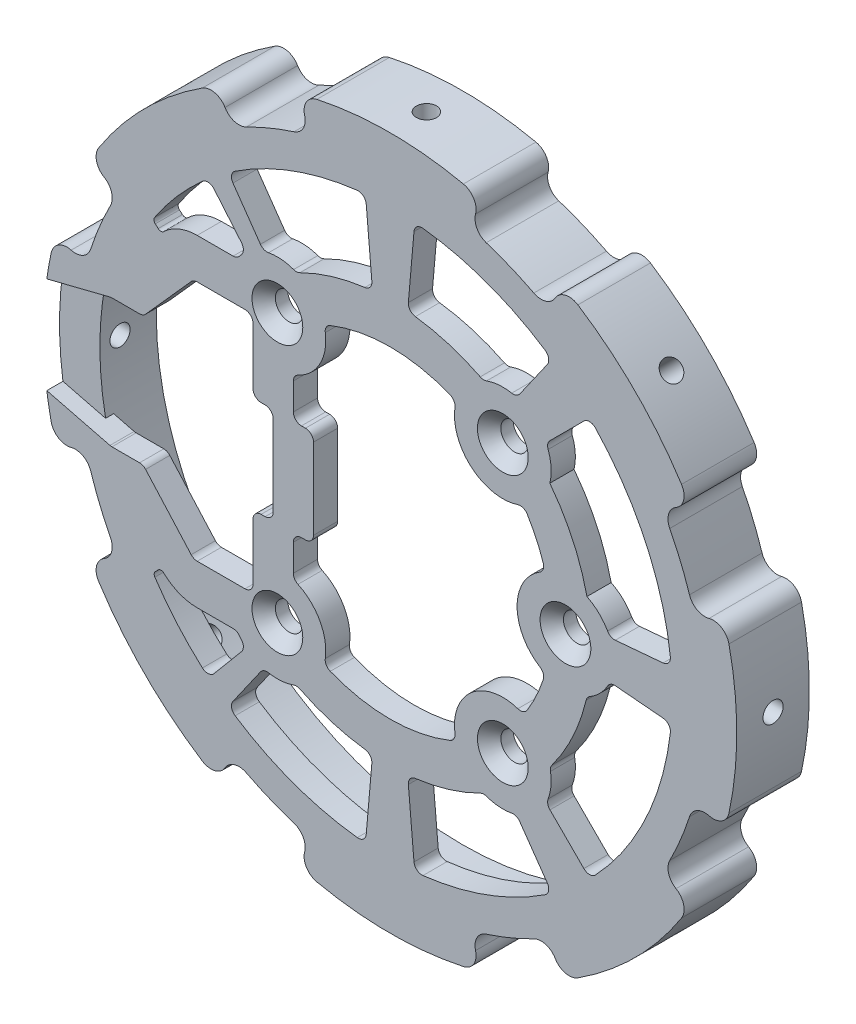
SolidWorks part; units mm, degrees
ref_plane "前视基准面" through (0, 0, 0) normal (0, 0, 1) x (1, 0, 0)
ref_plane "上视基准面" through (0, 0, 0) normal (0, 1, 0) x (1, 0, 0)
ref_plane "右视基准面" through (0, 0, 0) normal (1, 0, 0) x (0, 0, -1)
sketch "草图1" plane through (0, 0, 0) normal (0, 0, 1) x (1, 0, 0)
  line L16 (21.5, 37.2391) -> (19.5, 33.775)
  line L17 (11.1292, 41.5348) -> (10.0939, 37.6711)
  line L18 (-11.1292, 41.5348) -> (-10.0939, 37.6711)
  line L19 (37.2391, 21.5) -> (33.775, 19.5)
  line L20 (41.5348, 11.1292) -> (37.6711, 10.0939)
  line L21 (41.5348, -11.1292) -> (37.6711, -10.0939)
  line L22 (37.2391, -21.5) -> (33.775, -19.5)
  line L23 (21.5, -37.2391) -> (19.5, -33.775)
  line L24 (11.1292, -41.5348) -> (10.0939, -37.6711)
  line L25 (-11.1292, -41.5348) -> (-10.0939, -37.6711)
  line L26 (-21.5, -37.2391) -> (-19.5, -33.775)
  line L27 (-37.2391, -21.5) -> (-33.775, -19.5)
  line L28 (-41.5348, -11.1292) -> (-37.6711, -10.0939)
  line L29 (-41.5348, 11.1292) -> (-37.6711, 10.0939)
  line L30 (-37.2391, 21.5) -> (-33.775, 19.5)
  line L31 (-21.5, 37.2391) -> (-19.5, 33.775)
  circle A1 centre (0, 0) radius 38
  arc A6 (0, 43) -> (-11.1292, 41.5348) centre (0, 0) ccw
  arc A31 (0, 43) -> (11.1292, 41.5348) centre (0, 0) cw
  arc A32 (10.0939, 37.6711) -> (19.5, 33.775) centre (0, 0) cw
  arc A33 (30.4056, 30.4056) -> (21.5, 37.2391) centre (0, 0) ccw
  arc A34 (30.4056, 30.4056) -> (37.2391, 21.5) centre (0, 0) cw
  arc A35 (33.775, 19.5) -> (37.6711, 10.0939) centre (0, 0) cw
  arc A36 (43, 0) -> (41.5348, 11.1292) centre (0, 0) ccw
  arc A37 (43, 0) -> (41.5348, -11.1292) centre (0, 0) cw
  arc A38 (37.6711, -10.0939) -> (33.775, -19.5) centre (0, 0) cw
  arc A39 (30.4056, -30.4056) -> (37.2391, -21.5) centre (0, 0) ccw
  arc A40 (30.4056, -30.4056) -> (21.5, -37.2391) centre (0, 0) cw
  arc A41 (19.5, -33.775) -> (10.0939, -37.6711) centre (0, 0) cw
  arc A42 (0, -43) -> (11.1292, -41.5348) centre (0, 0) ccw
  arc A43 (0, -43) -> (-11.1292, -41.5348) centre (0, 0) cw
  arc A44 (-10.0939, -37.6711) -> (-19.5, -33.775) centre (0, 0) cw
  arc A45 (-30.4056, -30.4056) -> (-21.5, -37.2391) centre (0, 0) ccw
  arc A46 (-30.4056, -30.4056) -> (-37.2391, -21.5) centre (0, 0) cw
  arc A47 (-33.775, -19.5) -> (-37.6711, -10.0939) centre (0, 0) cw
  arc A48 (-43, 0) -> (-41.5348, -11.1292) centre (0, 0) ccw
  arc A49 (-43, 0) -> (-41.5348, 11.1292) centre (0, 0) cw
  arc A50 (-37.6711, 10.0939) -> (-33.775, 19.5) centre (0, 0) cw
  arc A51 (-30.4056, 30.4056) -> (-37.2391, 21.5) centre (0, 0) ccw
  arc A52 (-30.4056, 30.4056) -> (-21.5, 37.2391) centre (0, 0) cw
  arc A53 (-19.5, 33.775) -> (-10.0939, 37.6711) centre (0, 0) cw
  point P55 (0, 0)
  point P56 (0, 0)
  dimension "D1" = 8
extrude "凸台-拉伸1" add sketch "草图1" against normal blind 6
sketch "草图2" plane through (0, 0, 0) normal (0, 0, 1) x (1, 0, 0)
  line L16 (-11.1292, 41.5348) -> (-10.0939, 37.6711)
  line L17 (10.0939, 37.6711) -> (11.1292, 41.5348)
  line L18 (21.5, 37.2391) -> (19.5, 33.775)
  line L19 (33.775, 19.5) -> (37.2391, 21.5)
  line L20 (41.5348, 11.1292) -> (37.6711, 10.0939)
  line L21 (37.6711, -10.0939) -> (41.5348, -11.1292)
  line L22 (37.2391, -21.5) -> (33.775, -19.5)
  line L23 (19.5, -33.775) -> (21.5, -37.2391)
  line L24 (11.1292, -41.5348) -> (10.0939, -37.6711)
  line L25 (-10.0939, -37.6711) -> (-11.1292, -41.5348)
  line L26 (-21.5, -37.2391) -> (-19.5, -33.775)
  line L27 (-33.775, -19.5) -> (-37.2391, -21.5)
  line L28 (-41.5348, -11.1292) -> (-37.6711, -10.0939)
  line L29 (-37.6711, 10.0939) -> (-41.5348, 11.1292)
  line L30 (-37.2391, 21.5) -> (-33.775, 19.5)
  line L31 (-19.5, 33.775) -> (-21.5, 37.2391)
  arc A27 (0, 43) -> (11.1292, 41.5348) centre (0, 0) cw
  arc A28 (10.0939, 37.6711) -> (19.5, 33.775) centre (0, 0) cw
  arc A29 (0, 43) -> (-11.1292, 41.5348) centre (0, 0) ccw
  arc A30 (30.4056, 30.4056) -> (21.5, 37.2391) centre (0, 0) ccw
  arc A31 (30.4056, 30.4056) -> (37.2391, 21.5) centre (0, 0) cw
  arc A32 (33.775, 19.5) -> (37.6711, 10.0939) centre (0, 0) cw
  arc A33 (43, 0) -> (41.5348, 11.1292) centre (0, 0) ccw
  arc A34 (43, 0) -> (41.5348, -11.1292) centre (0, 0) cw
  arc A35 (37.6711, -10.0939) -> (33.775, -19.5) centre (0, 0) cw
  arc A36 (30.4056, -30.4056) -> (37.2391, -21.5) centre (0, 0) ccw
  arc A37 (30.4056, -30.4056) -> (21.5, -37.2391) centre (0, 0) cw
  arc A38 (19.5, -33.775) -> (10.0939, -37.6711) centre (0, 0) cw
  arc A39 (0, -43) -> (11.1292, -41.5348) centre (0, 0) ccw
  arc A40 (0, -43) -> (-11.1292, -41.5348) centre (0, 0) cw
  arc A41 (-10.0939, -37.6711) -> (-19.5, -33.775) centre (0, 0) cw
  arc A42 (-30.4056, -30.4056) -> (-21.5, -37.2391) centre (0, 0) ccw
  arc A43 (-30.4056, -30.4056) -> (-37.2391, -21.5) centre (0, 0) cw
  arc A44 (-33.775, -19.5) -> (-37.6711, -10.0939) centre (0, 0) cw
  arc A45 (-43, 0) -> (-41.5348, -11.1292) centre (0, 0) ccw
  arc A46 (-43, 0) -> (-41.5348, 11.1292) centre (0, 0) cw
  arc A47 (-37.6711, 10.0939) -> (-33.775, 19.5) centre (0, 0) cw
  arc A48 (-30.4056, 30.4056) -> (-37.2391, 21.5) centre (0, 0) ccw
  arc A49 (-30.4056, 30.4056) -> (-21.5, 37.2391) centre (0, 0) cw
  arc A50 (-19.5, 33.775) -> (-10.0939, 37.6711) centre (0, 0) cw
  point P43 (0, 0)
extrude "凸台-拉伸2" add sketch "草图2" along normal blind 3
hole_wizard "M3 锥坑平头的锥孔1" positions "3D草图2" profile "草图4" countersink size "M3" standard "BSI" end condition through all
sketch3d "3D草图2"
  point P58 (21.75, 0, 0)
  point P65 (21.75, 0, 3)
  point P79 (13.9806, -16.6615, 3)
  point P106 (13.9806, 16.6615, 3)
  point P128 (-13.9806, 16.6615, 3)
  point P130 (-13.9806, -16.6615, 3)
sketch "草图4" plane through (-13.9806, -16.6615, 3) normal (1, 0, 0) x (0, -1, 0)
  line L0 (0, 0) -> (0, 9)
  line L1 (0, 9) -> (1.7, 9)
  line L2 (1.7, 9) -> (1.7, 1.45)
  line L3 (1.7, 1.45) -> (3.15, 0)
  line L5 (3.15, 0) -> (0, 0)
  line L6 (-1.7, 1.45) -> (-3.15, 0) construction
  line L11 (0, -6.35) -> (0, 107.95) construction
  dimension "通孔孔直径" = 3.4
  dimension "通孔孔深度" = 9
  dimension "近端锥形沉头孔直径" = 6.3
  dimension "近端锥形沉头孔角度" = 90
hole_wizard "M3x0.5 螺纹孔1" positions "3D草图3" profile "草图5" tap size "M3x0.5" standard "BSI" end condition up to next
sketch3d "3D草图3"
  point P5 (0, -43, -1.5)
  point P13 (30.4056, -30.4056, -1.5)
  point P33 (30.4056, 30.4056, -1.5)
  point P43 (43, 0, -1.5)
  point P53 (-30.4056, 30.4056, -1.5)
  point P55 (-30.4056, -30.4056, -1.5)
  point P57 (43, 0, -1.5)
  point P72 (-43, 0, -1.5)
  point P77 (0, 43, -1.5)
sketch "草图5" plane through (0, -43, -1.5) normal (1, 0, 0) x (0, 0, -1)
  line L0 (0, 0) -> (0, 5)
  line L1 (0, 5) -> (1.25, 5)
  line L2 (1.25, 5) -> (1.25, 0)
  line L5 (1.25, 0) -> (0, 0)
  line L11 (0, -6.35) -> (0, 107.95) construction
  dimension "通孔螺纹孔钻头直径" = 2.5
  dimension "通孔螺纹孔钻头深度" = 5
cosmetic thread "孔螺蚊线1" parameters "D2"=3
cosmetic thread "孔螺蚊线2" parameters "D2"=3
cosmetic thread "孔螺蚊线3" parameters "D2"=3
cosmetic thread "孔螺蚊线4" parameters "D2"=3
cosmetic thread "孔螺蚊线5" parameters "D2"=3
cosmetic thread "孔螺蚊线6" parameters "D2"=3
sketch "草图6" plane through (0, 0, 0) normal (0, 0, 1) x (1, 0, 0)
  line L3 (-14.5, -6) -> (-14.5, 6)
  line L4 (-14.5, 6) -> (-17, 6)
  line L13 (-14.5, -6) -> (-17, -6)
  line L21 (-17, -15) -> (-17, -6)
  line L22 (-42.5793, 6) -> (-34.6246, 8)
  line L23 (-42.5793, -6) -> (-34.6246, -8)
  line L24 (-17, 6) -> (-17, 15)
  line L25 (-34.6246, 8) -> (-30.6246, 8)
  line L26 (-17, 15) -> (-24.3746, 15)
  line L27 (-30.6246, 8) -> (-24.3746, 15)
  line L28 (-34.6246, -8) -> (-30.6246, -8)
  line L29 (-30.6246, -8) -> (-24.3746, -15)
  line L30 (-24.3746, -15) -> (-17, -15)
  arc A2 (-41.5348, 11.1292) -> (-41.5348, -11.1292) centre (0, 0) ccw construction
  arc A3 (-42.5793, 6) -> (-42.5793, -6) centre (0, 0) ccw
extrude "切除-拉伸1" cut sketch "草图6" along normal blind 3
sketch "草图9" plane through (0, 0, 0) normal (0, 0, 1) x (1, 0, 0)
  line L0 (-34.6246, 8) -> (-42.5793, 6) construction
  line L1 (-37.2862, 7.3308) -> (-42.5793, 6) construction
  line L2 (-42.5793, 6) -> (-37.2862, 7.3308)
  line L3 (-42.5793, -6) -> (-37.2862, -7.3308)
  arc A0 (-37.2862, -7.3308) -> (-37.2862, 7.3308) centre (0, 0) cw
  arc A1 (-42.5793, -6) -> (-42.5793, 6) centre (0, 0) cw
extrude "凸台-拉伸3" add sketch "草图9" along normal blind 1
fillet "圆角1" radius 2 32 edges at (-21.5, 37.2391, -1.5) (-37.6711, 10.0939, -1.5) (-37.2391, 21.5, -1.5) (-33.775, 19.5, -1.5) (-41.5348, 11.1292, -1.5) (-37.2391, -21.5, -1.5) (-33.775, -19.5, -1.5) (-37.6711, -10.0939, -1.5) (-41.5348, -11.1292, -1.5) (-21.5, -37.2391, -1.5) (-19.5, -33.775, -1.5) (-11.1292, -41.5348, -1.5) (-10.0939, -37.6711, -1.5) (21.5, -37.2391, -1.5) (11.1292, -41.5348, -1.5) (10.0939, -37.6711, -1.5) (19.5, -33.775, -1.5) (37.2391, -21.5, -1.5) (33.775, -19.5, -1.5) (37.6711, 10.0939, -1.5) (37.6711, -10.0939, -1.5) (41.5348, -11.1292, -1.5) (41.5348, 11.1292, -1.5) (33.775, 19.5, -1.5) (37.2391, 21.5, -1.5) (10.0939, 37.6711, -1.5) (21.5, 37.2391, -1.5) (19.5, 33.775, -1.5) (11.1292, 41.5348, -1.5) (-10.0939, 37.6711, -1.5) (-11.1292, 41.5348, -1.5) (-19.5, 33.775, -1.5)
fillet "圆角2" radius 1 12 edges at (-24.3746, -15, 1.5) (-34.6246, -8, 1.5) (-30.6246, -8, 1.5) (-17, -15, 1.5) (-14.5, -6, 1.5) (-17, 15, 1.5) (-30.6246, 8, 1.5) (-17, -6, 1.5) (-14.5, 6, 1.5) (-17, 6, 1.5) (-24.3746, 15, 1.5) (-34.6246, 8, 1.5)
sketch "草图11" plane through (0, 0, 0) normal (0, 0, 1) x (1, 0, 0)
  line L0 (-12, 6) -> (-12, 10.9978)
  line L1 (-9.5, 6) -> (-9.5, -6)
  line L2 (-12, 6) -> (-9.5, 6)
  line L3 (-22.4976, 26.8116) -> (-17.8371, 21.2574)
  line L4 (-20.0753, 28.6702) -> (-15.6929, 22.4115)
  line L5 (-12, -6) -> (-12, -10.9978)
  line L6 (-12, -6) -> (-9.5, -6)
  line L8 (-3.0505, 34.8668) -> (-2.1789, 24.9046)
  line L9 (27.2559, -2.3844) -> (34.8668, -3.0503)
  line L10 (24.7489, -24.7486) -> (19.3462, -19.346)
  line L11 (-29.4425, 18.9246) -> (-28.4025, 17.9961)
  line L12 (-28.4025, -17.9961) -> (-29.3988, -18.9924)
  line L22 (-23.9269, 20) -> (-18.9655, 20)
  line L23 (4.95, 0) -> (-4.95, 0) construction
  line L24 (-3.0505, -34.8668) -> (-2.1789, -24.9046)
  line L26 (-20.0753, -28.6702) -> (-15.6929, -22.4115)
  line L27 (-22.4976, -26.8116) -> (-17.8371, -21.2574)
  line L30 (-23.9269, -20) -> (-18.9655, -20)
  line L31 (0, -4.95) -> (0, 4.95) construction
  line L32 (3.0505, -34.8668) -> (2.1789, -24.9046)
  line L33 (20.0753, -28.6702) -> (15.6929, -22.4115)
  line L34 (3.0505, 34.8668) -> (2.1789, 24.9046)
  line L35 (20.0753, 28.6702) -> (15.6929, 22.4115)
  line L36 (24.7489, 24.7486) -> (19.3462, 19.346)
  line L38 (27.2559, 2.3844) -> (34.8668, 3.0503)
  arc A2 (-8.1933, 18.2447) -> (8.1933, 18.2447) centre (0, 0) cw
  arc A3 (-12, 10.9978) -> (-8.1933, 18.2447) centre (-13.9806, 16.6615) ccw
  arc A4 (-12, -10.9978) -> (-8.1933, -18.2447) centre (-13.9806, -16.6615) cw
  arc A6 (8.1933, -18.2447) -> (16.5448, -11.237) centre (13.9806, -16.6615) cw
  arc A7 (19.2428, -5.4511) -> (19.2428, 5.4511) centre (21.75, 0) cw
  arc A12 (16.5448, 11.237) -> (19.2428, 5.4511) centre (0, 0) cw
  arc A13 (19.2428, -5.4511) -> (16.5448, -11.237) centre (0, 0) cw
  arc A15 (8.1933, -18.2447) -> (-8.1933, -18.2447) centre (0, 0) cw
  arc A16 (16.5448, 11.237) -> (8.1933, 18.2447) centre (13.9806, 16.6615) cw
  arc A19 (-20.0753, 28.6702) -> (-3.0505, 34.8668) centre (0, 0) cw
  arc A20 (-11.5761, 22.1581) -> (-2.1789, 24.9046) centre (0, 0) cw
  arc A22 (-11.5761, 22.1581) -> (-15.6929, 22.4115) centre (-13.9806, 16.6615) ccw
  arc A24 (24.7489, -24.7486) -> (34.8668, -3.0503) centre (0, 0) ccw
  arc A25 (27.2559, -2.3844) -> (24.4149, -5.3757) centre (21.75, 0) cw
  arc A26 (24.4149, -5.3757) -> (19.8114, -15.2478) centre (0, 0) cw
  arc A27 (19.3462, -19.346) -> (19.8114, -15.2478) centre (13.9806, -16.6615) ccw
  arc A28 (-22.4976, 26.8116) -> (-29.4425, 18.9246) centre (0, 0) ccw
  arc A29 (-22.4976, -26.8116) -> (-29.3988, -18.9924) centre (0, 0) cw
  arc A33 (-18.9655, 20) -> (-17.8371, 21.2574) centre (-13.9806, 16.6615) cw
  arc A35 (-23.9269, 20) -> (-28.4025, 17.9961) centre (-23.9269, 14) ccw
  arc A36 (-11.5761, -22.1581) -> (-2.1789, -24.9046) centre (0, 0) ccw
  arc A37 (-20.0753, -28.6702) -> (-3.0505, -34.8668) centre (0, 0) ccw
  arc A38 (-11.5761, -22.1581) -> (-15.6929, -22.4115) centre (-13.9806, -16.6615) cw
  arc A39 (-18.9655, -20) -> (-17.8371, -21.2574) centre (-13.9806, -16.6615) ccw
  arc A41 (-23.9269, -20) -> (-28.4025, -17.9961) centre (-23.9269, -14) cw
  arc A42 (20.0753, -28.6702) -> (3.0505, -34.8668) centre (0, 0) cw
  arc A43 (11.5761, -22.1581) -> (2.1789, -24.9046) centre (0, 0) cw
  arc A44 (11.5761, -22.1581) -> (15.6929, -22.4115) centre (13.9806, -16.6615) ccw
  arc A45 (11.5761, 22.1581) -> (2.1789, 24.9046) centre (0, 0) ccw
  arc A46 (20.0753, 28.6702) -> (3.0505, 34.8668) centre (0, 0) ccw
  arc A47 (11.5761, 22.1581) -> (15.6929, 22.4115) centre (13.9806, 16.6615) cw
  arc A48 (24.7489, 24.7486) -> (34.8668, 3.0503) centre (0, 0) cw
  arc A52 (27.2559, 2.3844) -> (24.4149, 5.3757) centre (21.75, 0) ccw
  arc A54 (24.4149, 5.3757) -> (19.8114, 15.2478) centre (0, 0) ccw
  arc A55 (19.3462, 19.346) -> (19.8114, 15.2478) centre (13.9806, 16.6615) cw
extrude "切除-拉伸2" cut sketch "草图11" along normal blind 10
fillet "圆角4" radius 1 50 edges at (-12, 10.9978, 1.5) (8.1933, 18.2447, 1.5) (-8.1933, 18.2447, 1.5) (19.2428, 5.4511, 1.5) (16.5448, 11.237, 1.5) (19.2428, -5.4511, 1.5) (16.5448, -11.237, 1.5) (8.1933, -18.2447, 1.5) (-12, -10.9978, 1.5) (-8.1933, -18.2447, 1.5) (34.8668, -3.0503, 1.5) (19.3462, -19.346, 1.5) (24.7489, -24.7486, 1.5) (19.8114, -15.2478, 1.5) (24.4149, -5.3757, 1.5) (27.2559, -2.3844, 1.5) (-18.9655, -20, 1.5) (-17.8371, -21.2574, 1.5) (20.0753, -28.6702, 1.5) (15.6929, -22.4115, 1.5) (3.0505, -34.8668, 1.5) (-2.1789, -24.9046, 1.5) (-20.0753, -28.6702, 1.5) (-3.0505, -34.8668, 1.5) (2.1789, -24.9046, 1.5) (11.5761, -22.1581, 1.5) (-11.5761, -22.1581, 1.5) (-15.6929, -22.4115, 1.5) (-12, -6, 1.5) (-9.5, -6, 1.5) (-9.5, 6, 1.5) (-12, 6, 1.5) (-18.9655, 20, 1.5) (-17.8371, 21.2574, 1.5) (-15.6929, 22.4115, 1.5) (-20.0753, 28.6702, 1.5) (-3.0505, 34.8668, 1.5) (-2.1789, 24.9046, 1.5) (-11.5761, 22.1581, 1.5) (3.0505, 34.8668, 1.5) (2.1789, 24.9046, 1.5) (11.5761, 22.1581, 1.5) (15.6929, 22.4115, 1.5) (20.0753, 28.6702, 1.5) (24.7489, 24.7486, 1.5) (34.8668, 3.0503, 1.5) (27.2559, 2.3844, 1.5) (19.3462, 19.346, 1.5) (-22.4976, 26.8116, 1.5) (-22.4976, -26.8116, 1.5)
fillet "圆角6" radius 0.5 4 edges at (-29.4425, 18.9246, 1.5) (-28.4025, -17.9961, 1.5) (-29.3988, -18.9924, 1.5) (-28.4025, 17.9961, 1.5)
